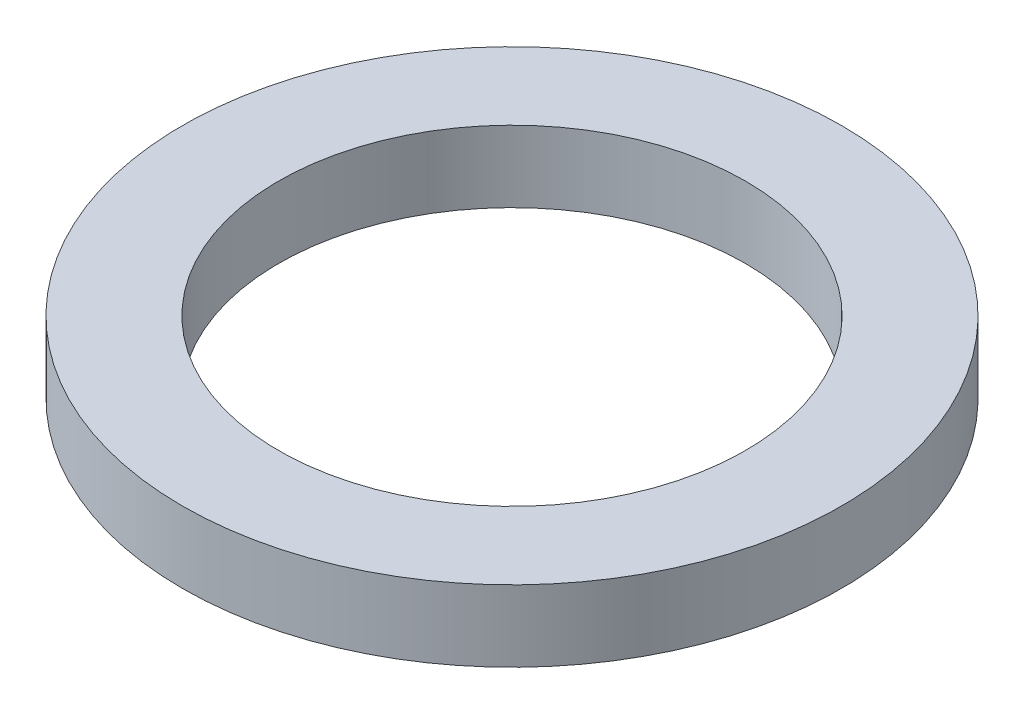
SolidWorks part; units mm, degrees
ref_plane "Front Plane" through (0, 0, 0) normal (0, 0, 1) x (1, 0, 0)
ref_plane "Top Plane" through (0, 0, 0) normal (0, 1, 0) x (1, 0, 0)
ref_plane "Right Plane" through (0, 0, 0) normal (1, 0, 0) x (0, 0, -1)
sketch "Sketch1" plane through (0, 0, 0) normal (0, 1, 0) x (1, 0, 0)
  circle A0 centre (0, 0) radius 60
  dimension "FLANGE_OD" = 120
extrude "Boss-Extrude1" add sketch "Sketch1" along normal blind 13
sketch "Sketch2" plane through (0, 0, 0) normal (0, 1, 0) x (1, 0, 0)
  circle A0 centre (0, 0) radius 42.5
  dimension "BORE_D" = 85
extrude "Cut-Extrude1" cut sketch "Sketch2" along normal through all
sketch "Sketch3" plane through (0, 13, 0) normal (0, 1, 0) x (1, 0, 0)
  circle A0 centre (0, 0) radius 22.7366 construction
  circle A1 centre (-22.7366, 0) radius 1.565
  dimension "BOLT_D" = 3.13
  dimension "BOLT_PCD" = 45.4731
extrude "Cut-Extrude2" cut sketch "Sketch3" against normal blind 12.379 rebuild error yes
pattern_circular "CirPattern1" count 3 over 360 rebuild error yes
